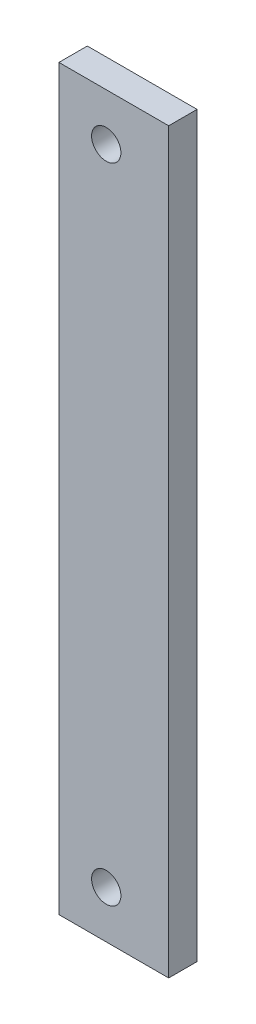
SolidWorks part; units mm, degrees
material "PET"
ref_plane "Front" through (0, 0, 0) normal (0, 0, 1) x (1, 0, 0)
ref_plane "Top" through (0, 0, 0) normal (0, 1, 0) x (1, 0, 0)
ref_plane "Right" through (0, 0, 0) normal (1, 0, 0) x (0, 0, -1)
sketch "Sketch1" plane through (0, 0, 0) normal (0, 0, 1) x (1, 0, 0)
  line L1 (2998.1721, 6301.4225) -> (3016.5871, 6301.4225)
  line L2 (2998.1721, 6301.4225) -> (2998.1721, 6425.2475)
  line L3 (2998.1721, 6425.2475) -> (3016.5871, 6425.2475)
  line L4 (3016.5871, 6301.4225) -> (3016.5871, 6425.2475)
extrude "Boss-Extrude1" add sketch "Sketch1" along normal blind 4.7625
hole_wizard "#8 Clearance Hole1" positions "Sketch3" profile "Sketch2" hole size "#8" standard "ANSI Inch" end condition through all
sketch "Sketch3" plane through (0, 0, 4.7625) normal (0, 0, 1) x (1, 0, 0)
  point P0 (3006.1096, 6417.31)
  point P3 (3006.1096, 6309.36)
sketch "Sketch2" plane through (3006.1096, 6417.31, 4.7625) normal (1, 0, 0) x (0, -1, 0)
  line L0 (0, 0) -> (0, 4.7625)
  line L1 (0, 4.7625) -> (2.4574, 4.7625)
  line L2 (2.4574, 4.7625) -> (2.4574, 0)
  line L5 (2.4574, 0) -> (0, 0)
  line L11 (0, -6.35) -> (0, 107.95) construction
  dimension "Thru Hole Dia." = 4.9149
  dimension "Thru Hole Depth" = 4.7625
